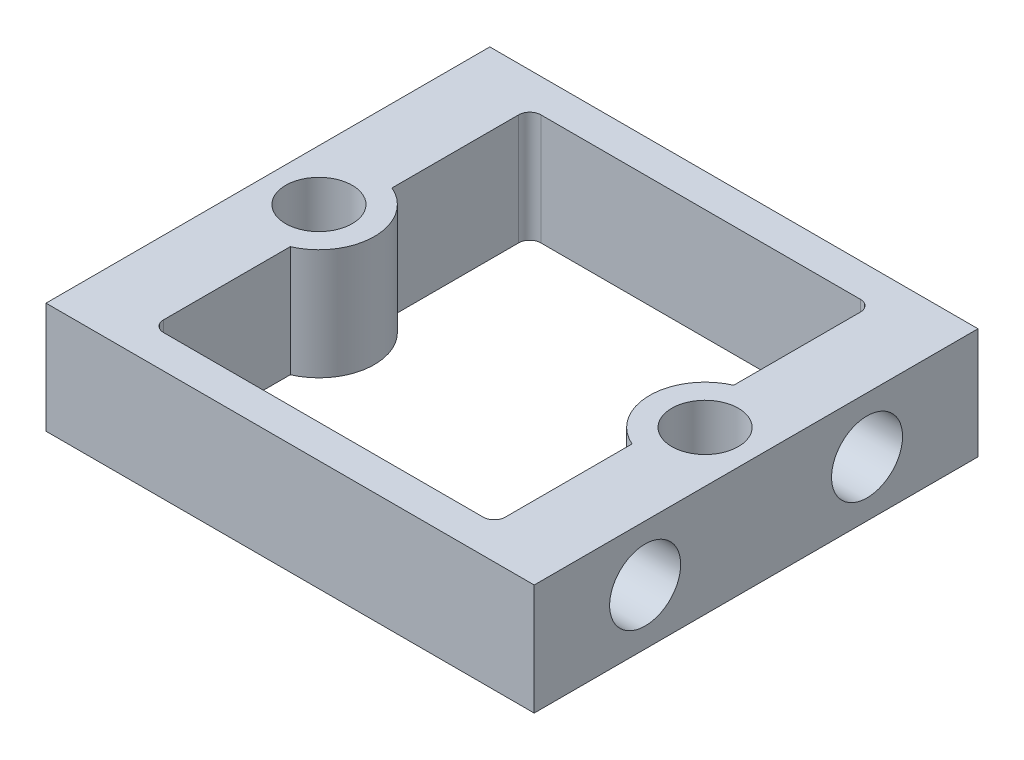
SolidWorks part; units mm, degrees
ref_plane "Front Plane" through (0, 0, 0) normal (0, 0, 1) x (1, 0, 0)
ref_plane "Top Plane" through (0, 0, 0) normal (0, 1, 0) x (1, 0, 0)
ref_plane "Right Plane" through (0, 0, 0) normal (1, 0, 0) x (0, 0, -1)
sketch "Sketch1" plane through (0, 0, 0) normal (0, 1, 0) x (1, 0, 0)
  line L1 (-11, 10) -> (11, 10)
  line L2 (-11, 10) -> (-11, -10)
  line L3 (-11, -10) -> (11, -10)
  line L4 (11, 10) -> (11, -10)
  line L5 (-11, 10) -> (11, -10) construction
  line L6 (-11, -10) -> (11, 10) construction
  point P0 (0, 0)
  dimension "D1" = 22
  dimension "D2" = 20
extrude "Boss-Extrude1" add sketch "Sketch1" along normal blind 5
sketch "Sketch2" plane through (0, 5, 0) normal (0, 1, 0) x (1, 0, 0)
  line L0 (8.7, -7.7) -> (8.7, -1.5) construction
  line L2 (-8.7, 7.7) -> (-8.7, 1.5) construction
  line L4 (11, -10) -> (11, 10)
  line L5 (11, 10) -> (-11, 10)
  line L6 (-11, 10) -> (-11, -10)
  line L7 (-11, -10) -> (11, -10)
  line L8 (11, -10) -> (11, 10) construction
  line L9 (11, 10) -> (-11, 10) construction
  line L10 (-11, 10) -> (-11, -10) construction
  line L11 (-11, -10) -> (11, -10) construction
  line L12 (-8.7, -1.5) -> (-8.7, -7.7) construction
  line L13 (-8.7, 7.7) -> (-8.7, -7.7) construction
  line L14 (8.7, 1.5) -> (8.7, 7.7) construction
  line L15 (8.7, -7.7) -> (8.7, 7.7) construction
  line L16 (7.7, -8.5) -> (7.7, -2.2913)
  line L18 (-7.7, -2.2913) -> (-7.7, -8.5)
  line L19 (-7.7, 8.5) -> (-7.7, 2.2913)
  line L21 (7.7, 2.2913) -> (7.7, 8.5)
  line L22 (-7.7, 8.5) -> (7.7, 8.5)
  line L23 (8.7, 7.7) -> (-8.7, 7.7) construction
  line L24 (-7.7, -8.5) -> (7.7, -8.5)
  line L25 (-8.7, -7.7) -> (8.7, -7.7) construction
  line L26 (-11, -10) -> (11, -10) construction
  arc A0 (-8.7, -1.5) -> (-8.7, 1.5) centre (-8.7, 0) ccw construction
  arc A1 (8.7, 1.5) -> (8.7, -1.5) centre (8.7, 0) ccw construction
  arc A2 (7.7, 2.2913) -> (7.7, -2.2913) centre (8.7, 0) ccw
  arc A3 (-7.7, -2.2913) -> (-7.7, 2.2913) centre (-8.7, 0) ccw
  point P11 (-7.2, 0)
  point P15 (-11, 0)
  dimension "D3" = 3
  dimension "D4" = 17.4
  dimension "D9" = 1
  dimension "D10" = 1
  dimension "D2" = 17.4
  dimension "D5" = 1
  dimension "D6" = 1
  dimension "D7" = 1.5
  dimension "D8" = 1.5
  dimension "D1" = 0
hole_wizard "M3 Clearance Hole1" positions "Sketch3" profile "Sketch4" hole size "M3" standard "ANSI Metric" end condition through all
sketch "Sketch3" plane through (0, 5, 0) normal (0, 1, 0) x (1, 0, 0)
  point P0 (-8.7, 0)
  point P3 (8.7, 0)
sketch "Sketch4" plane through (-8.7, 5, 0) normal (1, 0, 0) x (0, 0, 1)
  line L0 (0, 0) -> (0, 5)
  line L1 (0, 5) -> (1.5, 5)
  line L2 (1.5, 5) -> (1.5, 0)
  line L5 (1.5, 0) -> (0, 0)
  line L11 (0, -6.35) -> (0, 107.95) construction
  dimension "Thru Hole Dia." = 3
  dimension "Thru Hole Depth" = 5
extrude "Cut-Extrude1" cut sketch "Sketch2" against normal through all
sketch "Sketch5" plane through (11, 0, 0) normal (1, 0, 0) x (0, 0, -1)
  line L0 (-5, 2.5) -> (5, 2.5) construction
  line L1 (-10, 5) -> (10, 5) construction
  line L2 (10, 5) -> (10, 0) construction
  point P0 (-5, 2.5)
  point P1 (5, 2.5)
  point P6 (0, 5)
  point P7 (0, 2.5)
  point P11 (10, 2.5)
  dimension "D1" = 10
hole_wizard "Ø3.2 (3.2) heat set" positions "Sketch6" profile "Sketch7" hole size "Ø3.2" standard "ANSI Metric" end condition up to next
sketch "Sketch6" plane through (11, 0, 0) normal (1, 0, 0) x (0, 0, -1)
  point P0 (-5, 2.5)
  point P3 (5, 2.5)
sketch "Sketch7" plane through (11, 2.5, 5) normal (0, 1, 0) x (0, 0, -1)
  line L0 (0, 0) -> (0, 3.3)
  line L1 (0, 3.3) -> (1.6, 3.3)
  line L2 (1.6, 3.3) -> (1.6, 0)
  line L5 (1.6, 0) -> (0, 0)
  line L11 (0, -6.35) -> (0, 107.95) construction
  dimension "Thru Hole Dia." = 3.2
  dimension "Thru Hole Depth" = 3.3
fillet "Fillet1" radius 0.5 4 edges at (7.7, 2.5, 8.5) (7.7, 2.5, -8.5) (-7.7, 2.5, -8.5) (-7.7, 2.5, 8.5)
